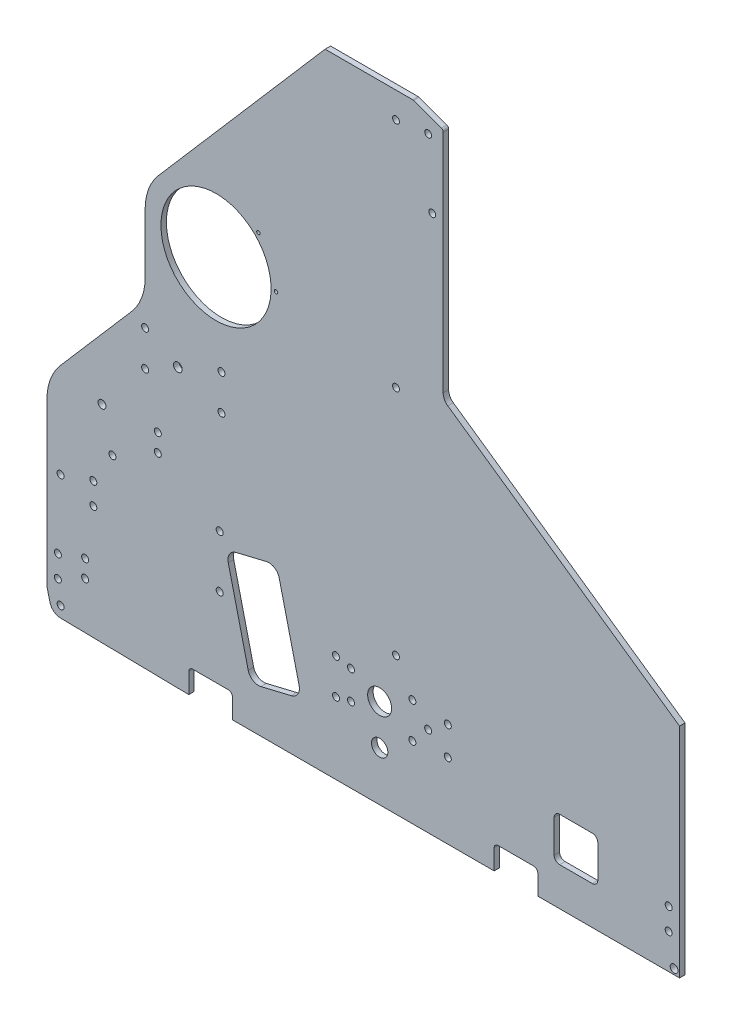
SolidWorks part; units mm, degrees
ref_plane "Front Plane" through (0, 0, 0) normal (0, 0, 1) x (1, 0, 0)
ref_plane "Top Plane" through (0, 0, 0) normal (0, 1, 0) x (1, 0, 0)
ref_plane "Right Plane" through (0, 0, 0) normal (1, 0, 0) x (0, 0, -1)
sketch "Sketch1" plane through (0, 0, 0) normal (0, 0, 1) x (1, 0, 0)
  line L0 (82.55, -20.32) -> (82.55, -6.35)
  line L2 (0, 0) -> (0, 157.48)
  line L4 (368.3, -20.32) -> (368.3, 106.68)
  line L5 (82.55, -6.35) -> (107.95, -6.35)
  line L6 (107.95, -6.35) -> (107.95, -20.32)
  line L7 (107.95, -20.32) -> (260.35, -20.32)
  line L8 (260.35, -20.32) -> (260.35, -6.35)
  line L9 (260.35, -6.35) -> (285.75, -6.35)
  line L10 (285.75, -6.35) -> (285.75, -20.32)
  line L11 (285.75, -20.32) -> (368.3, -20.32)
  line L12 (361.95, 12.7) -> (368.3, 12.7) construction
  line L13 (0, 0) -> (6.35, 0) construction
  line L14 (0.1896, -7.8901) -> (1.7771, -14.2401)
  line L15 (7.8295, -19.0491) -> (82.55, -20.32)
  line L16 (0, 0) -> (0, -6.35)
  line L17 (76.2, 141.605) -> (79.375, 141.605) construction
  line L18 (57.15, 131.2863) -> (101.6, 131.2862) construction
  line L19 (57.15, 131.2863) -> (57.15, 151.9238) construction
  line L20 (101.6, 131.2862) -> (101.6, 151.9237) construction
  line L21 (57.15, 151.9238) -> (101.6, 151.9237) construction
  line L22 (57.15, 131.2863) -> (101.6, 151.9237) construction
  line L23 (101.6, 131.2862) -> (57.15, 151.9238) construction
  line L25 (203.2, 59.805) -> (203.2, 194.805) construction
  line L26 (203.2, 194.805) -> (203.2, 329.805) construction
  line L27 (355.6, 332.105) -> (330.2, 332.105) construction
  line L28 (330.2, 332.105) -> (330.2, 217.805) construction
  line L29 (330.2, 217.805) -> (355.6, 217.805) construction
  line L30 (355.6, 217.805) -> (355.6, 332.105) construction
  line L31 (203.2, 344.805) -> (203.2, 194.805) construction
  line L32 (50.8, 332.105) -> (76.2, 332.105) construction
  line L33 (76.2, 332.105) -> (76.2, 217.805) construction
  line L34 (50.8, 217.805) -> (50.8, 332.105) construction
  line L35 (76.2, 217.805) -> (50.8, 217.805) construction
  line L36 (213.2, 344.805) -> (230.6638, 338.455)
  line L37 (203.2, 344.805) -> (161.925, 344.805)
  line L38 (203.2, 344.805) -> (213.2, 344.805)
  line L39 (348.5362, 344.805) -> (413.4623, 344.805)
  line L40 (348.5362, 344.805) -> (230.6638, 344.805) construction
  line L42 (161.925, 344.805) -> (0, 157.48)
  line L44 (230.6638, 338.455) -> (230.6638, 202.565)
  line L45 (230.6638, 202.565) -> (368.3, 106.68)
  line L46 (213.2, 344.805) -> (-141.0713, 344.805) construction
  circle A0 centre (6.35, 0) radius 2.032
  circle A1 centre (6.35, 12.7) radius 2.032
  circle A2 centre (361.95, 0) radius 2.032
  circle A3 centre (361.95, 12.7) radius 2.032
  arc A5 (1.7771, -14.2401) -> (7.8295, -19.0491) centre (7.9375, -12.7) ccw
  circle A6 centre (7.9375, -12.7) radius 2.032
  arc A7 (0, -6.35) -> (0.1896, -7.8901) centre (6.35, -6.35) ccw
  circle A8 centre (38.1, 78.105) radius 2.032
  circle A9 centre (76.2, 141.605) radius 2.54
  circle A10 centre (101.6, 131.2862) radius 2.032
  circle A11 centre (101.6, 151.9237) radius 2.032
  circle A12 centre (57.15, 151.9238) radius 2.032
  circle A13 centre (57.15, 131.2863) radius 2.032
  circle A15 centre (203.2, 59.805) radius 2
  circle A16 centre (203.2, 194.805) radius 2
  circle A17 centre (203.2, 329.805) radius 2
  circle A18 centre (63.5, 313.055) radius 2.032
  circle A20 centre (355.6, 332.105) radius 2.032
  circle A21 centre (330.2, 332.105) radius 2.032
  circle A22 centre (355.6, 217.805) radius 2.032
  circle A23 centre (330.2, 217.805) radius 2.032
  circle A24 centre (50.8, 332.105) radius 2.032
  circle A25 centre (76.2, 332.105) radius 2.032
  circle A26 centre (50.8, 217.805) radius 2.032
  circle A27 centre (76.2, 217.805) radius 2.032
  circle A28 centre (221.9319, 332.105) radius 2
  circle A29 centre (224.3138, 293.243) radius 2.032
  point P82 (203.2, 344.805)
  point P83 (221.9319, 341.63)
  dimension "D6" = 4.064
  dimension "D10" = 6.35
  dimension "D11" = 4.064
  dimension "D17" = 38.1
  dimension "D27" = 4
  dimension "D31" = 4.064
  dimension "D32" = 41.275
  dimension "D36" = 4.064
  dimension "D47" = 45.212
  dimension "D48" = 4.064
  dimension "D25" = 5.08
  dimension "D2" = 127
  dimension "D3" = 13.97
  dimension "D4" = 25.4
  dimension "D5" = 152.4
  dimension "D7" = 12.7
  dimension "D8" = 6.35
  dimension "D9" = 20.32
  dimension "D12" = 12.7
  dimension "D13" = 1.5875
  dimension "D14" = 82.55
  dimension "D15" = 368.3
  dimension "D16" = 6.35
  dimension "D18" = 98.425
  dimension "D19" = 38.1
  dimension "D20" = 63.5
  dimension "D21" = 3.175
  dimension "D22" = 270
  dimension "D23" = 20.6375
  dimension "D24" = 44.45
  dimension "D28" = 135
  dimension "D29" = 12.7
  dimension "D30" = 15
  dimension "D33" = 63.5
  dimension "D34" = 27.4638
  dimension "D37" = 114.3
  dimension "D38" = 25.4
  dimension "D39" = 12.7
  dimension "D40" = 157.48
  dimension "D41" = 142.24
  dimension "D42" = 365.125
  dimension "D43" = 10
  dimension "D44" = 6.35
  dimension "D45" = 31.75
  dimension "D46" = 6.35
  dimension "D49" = 6.35
  dimension "D50" = 203.2
extrude "Boss-Extrude1" add sketch "Sketch1" along normal blind 3.175 contours L16 A7 L14 A5 L15 L2 A0 A1 A6 region at (171.4043, 119.6328, 0)
fillet "Fillet1" radius 2.286 4 edges at (285.75, -6.35, 1.5875) (107.95, -6.35, 1.5875) (260.35, -6.35, 1.5875) (82.55, -6.35, 1.5875)
fillet "Fillet2" radius 6.35 1 edges at (230.6638, 202.565, 1.5875)
sketch "Sketch2" plane through (0, 0, 0) normal (0, 0, -1) x (-1, 0, 0)
  circle A0 centre (-100.5528, 71.086) radius 2.032 construction
  circle A1 centre (-100.5528, 40.606) radius 2.032 construction
  circle A2 centre (-22.225, 18.2025) radius 2.032 construction
  circle A3 centre (-22.225, 8.0425) radius 2.032 construction
  circle A4 centre (-100.5528, 71.086) radius 2.032
  circle A5 centre (-100.5528, 40.606) radius 2.032
  circle A6 centre (-22.225, 18.2025) radius 2.032
  circle A7 centre (-22.225, 8.0425) radius 2.032
extrude "Cut-Extrude1" cut sketch "Sketch2" against normal through all
fillet "Fillet3" radius 1.5875 2 edges at (230.6638, 338.455, 1.5875) (213.2, 344.805, 1.5875)
sketch "Sketch3" plane through (0, 0, 3.175) normal (0, 0, 1) x (1, 0, 0)
  line L0 (132.9524, 63.2646) -> (132.7215, 64.2281) construction
  line L1 (128.3815, 66.8898) -> (110.6829, 62.6472) construction
  line L2 (114.5132, 58.4237) -> (126.8822, 61.3887) construction
  line L3 (108.0212, 58.3072) -> (108.2522, 57.3436) construction
  line L4 (131.2006, 57.703) -> (140.0164, 20.9266) construction
  line L5 (144.0993, 16.7636) -> (132.9524, 63.2646) construction
  line L6 (108.2522, 57.3436) -> (119.3991, 10.8427) construction
  line L7 (121.1509, 16.4042) -> (112.3351, 53.1807) construction
  line L8 (119.3991, 10.8427) -> (119.6301, 9.8791) construction
  line L9 (144.3303, 15.8001) -> (144.0993, 16.7636) construction
  line L10 (137.8383, 15.6835) -> (125.4694, 12.7185) construction
  line L11 (123.9701, 7.2175) -> (141.6687, 11.4601) construction
  line L12 (132.9524, 63.2646) -> (132.7215, 64.2281)
  line L13 (128.3815, 66.8898) -> (110.6829, 62.6472)
  line L14 (114.5132, 58.4237) -> (126.8822, 61.3887)
  line L15 (108.0212, 58.3072) -> (108.2522, 57.3436)
  line L16 (131.2006, 57.703) -> (140.0164, 20.9266)
  line L17 (144.0993, 16.7636) -> (132.9524, 63.2646)
  line L18 (108.2522, 57.3436) -> (119.3991, 10.8427)
  line L19 (121.1509, 16.4042) -> (112.3351, 53.1807)
  line L20 (119.3991, 10.8427) -> (119.6301, 9.8791)
  line L21 (144.3303, 15.8001) -> (144.0993, 16.7636)
  line L22 (137.8383, 15.6835) -> (125.4694, 12.7185)
  line L23 (123.9701, 7.2175) -> (141.6687, 11.4601)
  line L24 (127.7894, 69.3598) -> (110.0908, 65.1172)
  line L25 (105.5512, 57.7151) -> (105.7822, 56.7515)
  line L26 (105.7822, 56.7515) -> (116.9291, 10.2506)
  line L27 (116.9291, 10.2506) -> (117.16, 9.287)
  line L28 (124.5622, 4.7475) -> (142.2608, 8.9901)
  line L29 (146.8003, 16.3922) -> (146.5694, 17.3557)
  line L30 (146.5694, 17.3557) -> (135.4225, 63.8567)
  line L31 (135.4225, 63.8567) -> (135.1915, 64.8202)
  line L32 (14.605, -0.1369) -> (103.7278, 32.3011) construction
  line L33 (14.605, -0.1369) -> (103.7278, 32.3011)
  line L35 (-39.6666, 74.7152) -> (103.7278, 126.9065) construction
  arc A0 (132.7215, 64.2281) -> (128.6308, 66.9403) centre (129.2206, 63.3889) ccw construction
  arc A1 (110.6829, 62.6472) -> (110.4377, 62.5791) centre (111.522, 59.1463) ccw construction
  arc A2 (128.6308, 66.9403) -> (128.3815, 66.8898) centre (129.2206, 63.3889) ccw construction
  arc A3 (110.4377, 62.5791) -> (108.0212, 58.3072) centre (111.522, 59.1463) ccw construction
  arc A4 (119.6301, 9.8791) -> (123.7207, 7.167) centre (123.1309, 10.7183) ccw construction
  arc A5 (141.9139, 11.5281) -> (144.3303, 15.8001) centre (140.8295, 14.9609) ccw construction
  arc A6 (141.6687, 11.4601) -> (141.9139, 11.5281) centre (140.8295, 14.9609) ccw construction
  arc A7 (123.7207, 7.167) -> (123.9701, 7.2175) centre (123.1309, 10.7183) ccw construction
  arc A8 (132.7215, 64.2281) -> (128.6308, 66.9403) centre (129.2206, 63.3889) ccw
  arc A9 (110.6829, 62.6472) -> (110.4377, 62.5791) centre (111.522, 59.1463) ccw
  arc A10 (128.6308, 66.9403) -> (128.3815, 66.8898) centre (129.2206, 63.3889) ccw
  arc A11 (110.4377, 62.5791) -> (108.0212, 58.3072) centre (111.522, 59.1463) ccw
  arc A12 (119.6301, 9.8791) -> (123.7207, 7.167) centre (123.1309, 10.7183) ccw
  arc A13 (141.9139, 11.5281) -> (144.3303, 15.8001) centre (140.8295, 14.9609) ccw
  arc A14 (141.6687, 11.4601) -> (141.9139, 11.5281) centre (140.8295, 14.9609) ccw
  arc A15 (123.7207, 7.167) -> (123.9701, 7.2175) centre (123.1309, 10.7183) ccw
  arc A16 (110.0908, 65.1172) -> (109.6726, 65.0012) centre (111.522, 59.1463) ccw
  arc A17 (109.6726, 65.0012) -> (105.5512, 57.7151) centre (111.522, 59.1463) ccw
  arc A18 (117.16, 9.287) -> (124.1369, 4.6613) centre (123.1309, 10.7183) ccw
  arc A19 (124.1369, 4.6613) -> (124.5622, 4.7475) centre (123.1309, 10.7183) ccw
  arc A20 (142.2608, 8.9901) -> (142.679, 9.1061) centre (140.8295, 14.9609) ccw
  arc A21 (142.679, 9.1061) -> (146.8003, 16.3922) centre (140.8295, 14.9609) ccw
  arc A22 (135.1915, 64.8202) -> (128.2147, 69.446) centre (129.2206, 63.3889) ccw
  arc A23 (128.2147, 69.446) -> (127.7894, 69.3598) centre (129.2206, 63.3889) ccw
  circle A24 centre (64.5259, 102.9405) radius 2.032 construction
  circle A25 centre (64.5259, 92.5258) radius 2.032 construction
  circle A26 centre (133.35, 208.2281) radius 1.016 construction
  circle A33 centre (26.9875, 46.9531) radius 2.032
  circle A34 centre (26.9875, 59.6531) radius 2.032
  circle A35 centre (7.9375, 53.3031) radius 2.032
  circle A36 centre (7.9375, 53.3031) radius 2.032 construction
  circle A37 centre (32.0306, 100.8109) radius 31.75 construction
  circle A38 centre (32.0306, 100.8109) radius 2.286
  circle A39 centre (123.1207, 232.9238) radius 1.016 construction
  circle A40 centre (64.5259, 102.9405) radius 2.032
  circle A41 centre (64.5259, 92.5258) radius 2.032
  circle A42 centre (133.35, 208.2281) radius 1.016
  circle A43 centre (123.1207, 232.9238) radius 1.016
  circle A44 centre (26.9875, 59.6531) radius 2.032 construction
  circle A45 centre (26.9875, 46.9531) radius 2.032 construction
  ellipse E0 centre (124.5975, 48.8487) end of major axis (128.5376, 61.3578) minor radius 6 (131.2006, 57.703) -> (126.8822, 61.3887) ccw construction
  ellipse E1 centre (122.2349, 48.2824) end of major axis (113.0518, 57.6456) minor radius 6 (114.5132, 58.4237) -> (112.3351, 53.1807) ccw construction
  ellipse E2 centre (127.7541, 25.2585) end of major axis (131.6942, 37.7675) minor radius 6 (121.1509, 16.4042) -> (125.4694, 12.7185) ccw construction
  ellipse E3 centre (130.1166, 25.8248) end of major axis (139.2998, 16.4616) minor radius 6 (137.8383, 15.6835) -> (140.0164, 20.9266) ccw construction
  ellipse E4 centre (124.5975, 48.8487) end of major axis (128.5376, 61.3578) minor radius 6 (131.2006, 57.703) -> (126.8822, 61.3887) ccw
  ellipse E5 centre (122.2349, 48.2824) end of major axis (131.4181, 38.9192) minor radius 6 (114.5132, 58.4237) -> (112.3351, 53.1807) ccw
  ellipse E6 centre (127.7541, 25.2585) end of major axis (123.814, 12.7495) minor radius 6 (121.1509, 16.4042) -> (125.4694, 12.7185) ccw
  ellipse E7 centre (130.1166, 25.8248) end of major axis (139.2998, 16.4616) minor radius 6 (137.8383, 15.6835) -> (140.0164, 20.9266) ccw
  point P115 (32.0306, 100.8109)
  dimension "D3" = 63.5
  dimension "D4" = 4.572
  dimension "D2" = 88.9
  dimension "D1" = 2.54
extrude "Cut-Extrude2" cut sketch "Sketch3" against normal through all contours A22 A23 L24 A16 A17 L25 L26 L27 A18 A19 L28 A20 A21 L29 L30 L31 A15 A12 L20 L18 L15 A11 A9 L13 A10 A8 L12 L17 L21 A13 A14 L23 | A12 A15 L23 A14 A13 L21 L17 L12 A8 A10 L13 A9 A11 L15 L18 L20 E7 L22 E6 L19 E5 L14 E4 L16 | L22 E7 L16 E4 L14 E5 L19 E6 | A38 | A41 | A40 | A35 | A34 | A33 | A43 | A42 region at (137.844, 39.8506, 3.175) region at (126.1758, 37.0536, 3.175) region at (128.1544, 68.6508, 3.175) region at (32.0306, 100.8109, 3.175) region at (64.5259, 102.9405, 3.175) region at (64.5259, 92.5258, 3.175)
sketch "Sketch4" plane through (0, 0, 3.175) normal (0, 0, 1) x (1, 0, 0)
  line L0 (57.15, 151.9238) -> (101.6, 151.9237) construction
  line L1 (168.275, 21.4312) -> (212.725, 21.4312) construction
  line L2 (168.275, 21.4312) -> (168.275, 42.0687) construction
  line L3 (168.275, 42.0687) -> (212.725, 42.0687) construction
  line L4 (212.725, 21.4312) -> (212.725, 42.0687) construction
  line L5 (168.275, 21.4312) -> (212.725, 42.0687) construction
  line L6 (168.275, 42.0687) -> (212.725, 21.4312) construction
  line L7 (57.15, 131.2863) -> (57.15, 151.9238) construction
  line L8 (107.95, -20.32) -> (260.35, -20.32) construction
  line L9 (193.675, 31.75) -> (177.005, 31.75) construction
  line L10 (190.5, 31.75) -> (193.675, 31.75) construction
  line L11 (6.35, 12.7) -> (361.95, 12.7) construction
  line L12 (107.95, -6.35) -> (107.95, -20.32) construction
  line L13 (193.675, 31.75) -> (220.6625, 31.75) construction
  line L14 (177.005, 23.4569) -> (177.005, 40.0431) construction
  line L15 (213.2, 44.805) -> (193.2, 44.805) construction
  line L16 (213.2, 44.805) -> (213.2, 344.805) construction
  line L17 (213.2, 344.805) -> (193.2, 344.805) construction
  line L18 (193.2, 44.805) -> (193.2, 344.805) construction
  line L19 (213.2, 44.805) -> (193.2, 344.805) construction
  line L20 (213.2, 344.805) -> (193.2, 44.805) construction
  line L21 (226.9319, 332.105) -> (226.9319, 31.75) construction
  line L22 (237.33, 40.0431) -> (233.3612, 40.0431) construction
  line L23 (237.33, 23.4569) -> (233.3612, 23.4569) construction
  circle A0 centre (168.275, 42.0687) radius 2.032
  circle A1 centre (212.725, 42.0687) radius 2.032
  circle A2 centre (212.725, 21.4312) radius 2.032
  circle A3 centre (168.275, 21.4312) radius 2.032
  circle A4 centre (193.675, 31.75) radius 6.985
  circle A7 centre (220.6625, 31.75) radius 14.2875 construction
  circle A8 centre (193.675, 31.75) radius 12.7 construction
  circle A9 centre (177.005, 40.0431) radius 2.032
  circle A10 centre (177.005, 23.4569) radius 2.032
  circle A11 centre (237.33, 40.0431) radius 2.032 construction
  circle A12 centre (237.33, 23.4569) radius 2.032 construction
  circle A13 centre (193.675, 8.4667) radius 4.7625
  circle A14 centre (221.9319, 31.75) radius 2.032
  circle A15 centre (221.9319, 31.75) radius 5 construction
  circle A16 centre (221.9319, 332.105) radius 5 construction
  circle A17 centre (233.3612, 23.4569) radius 2.032
  circle A18 centre (233.3612, 40.0431) radius 2.032
  point P0 (190.5, 31.75)
  point P26 (203.2, 194.805)
  point P38 (177.005, 31.75)
  dimension "D1" = 4.064
  dimension "D4" = 13.97
  dimension "D7" = 9.525
  dimension "D10" = 25.4
  dimension "D11" = 28.575
  dimension "D16" = 10
  dimension "D17" = 4.064
  dimension "D18" = 10
  dimension "D2" = 52.07
  dimension "D3" = 3.175
  dimension "D5" = 82.55
  dimension "D6" = 26.9875
  dimension "D8" = 20
  dimension "D9" = 300
  dimension "D12" = 16.67
  dimension "D13" = 16.5862
  dimension "D14" = 60.325
  dimension "D15" = 23.2833
  dimension "D19" = 3.9688
extrude "Cut-Extrude3" cut sketch "Sketch4" against normal through all
sketch "Sketch5" plane through (0, 0, -187.325) normal (0, 0, -1) x (-1, 0, 0)
  line L0 (-57.15, 223.5947) -> (-57.15, 165.3337)
  line L1 (-161.925, 344.805) -> (-52.7201, 218.4699) construction
  line L2 (-57.15, 165.3337) -> (0, 99.219)
  line L3 (0, -6.35) -> (0, 157.48) construction
  line L4 (-50.4199, 215.8089) -> (0, 157.48) construction
  line L5 (-50.4199, 215.8089) -> (0, 157.48) construction
  line L6 (-57.15, 223.5947) -> (0, 157.48)
  line L7 (0, 157.48) -> (0, 99.219)
  circle A0 centre (-98.425, 208.2281) radius 32.0675
  circle A1 centre (-365.125, -17.145) radius 2.286 construction
  circle A2 centre (-365.125, -17.145) radius 2.286
  dimension "D3" = 64.135
  dimension "D1" = 38.1
  dimension "D2" = 57.15
  dimension "D4" = 41.275
  dimension "D5" = 41.275
extrude "Cut-Extrude5" cut sketch "Sketch5" against normal through all contours A0 | L7 L6 L0 L2 | A2 region at (28.575, 161.4068, -187.325) region at (98.425, 208.2281, -187.325)
fillet "Fillet4" radius 31.75 3 edges at (0, 99.219, 1.5875) (57.15, 165.3337, 1.5875) (57.15, 223.5947, 1.5875)
sketch "Sketch6" plane through (0, 0, 3.175) normal (0, 0, 1) x (1, 0, 0)
  line L0 (285.75, -20.32) -> (368.3, -20.32) construction
  line L1 (298.45, 27.305) -> (317.5, 27.305)
  line L2 (295.275, 24.13) -> (295.275, 5.08)
  line L3 (298.45, 1.905) -> (317.5, 1.905)
  line L4 (320.675, 24.13) -> (320.675, 5.08)
  line L5 (295.275, 27.305) -> (320.675, 1.905) construction
  line L6 (295.275, 1.905) -> (320.675, 27.305) construction
  line L7 (368.3, -20.32) -> (368.3, 106.68) construction
  arc A0 (295.275, 5.08) -> (298.45, 1.905) centre (298.45, 5.08) ccw
  arc A1 (317.5, 1.905) -> (320.675, 5.08) centre (317.5, 5.08) ccw
  arc A2 (317.5, 27.305) -> (320.675, 24.13) centre (317.5, 24.13) cw
  arc A3 (298.45, 27.305) -> (295.275, 24.13) centre (298.45, 24.13) ccw
  point P0 (307.975, 14.605)
  dimension "D2" = 3.175
  dimension "D1" = 25.4
  dimension "D3" = 22.225
  dimension "D4" = 47.625
extrude "Cut-Extrude6" cut sketch "Sketch6" against normal through all
